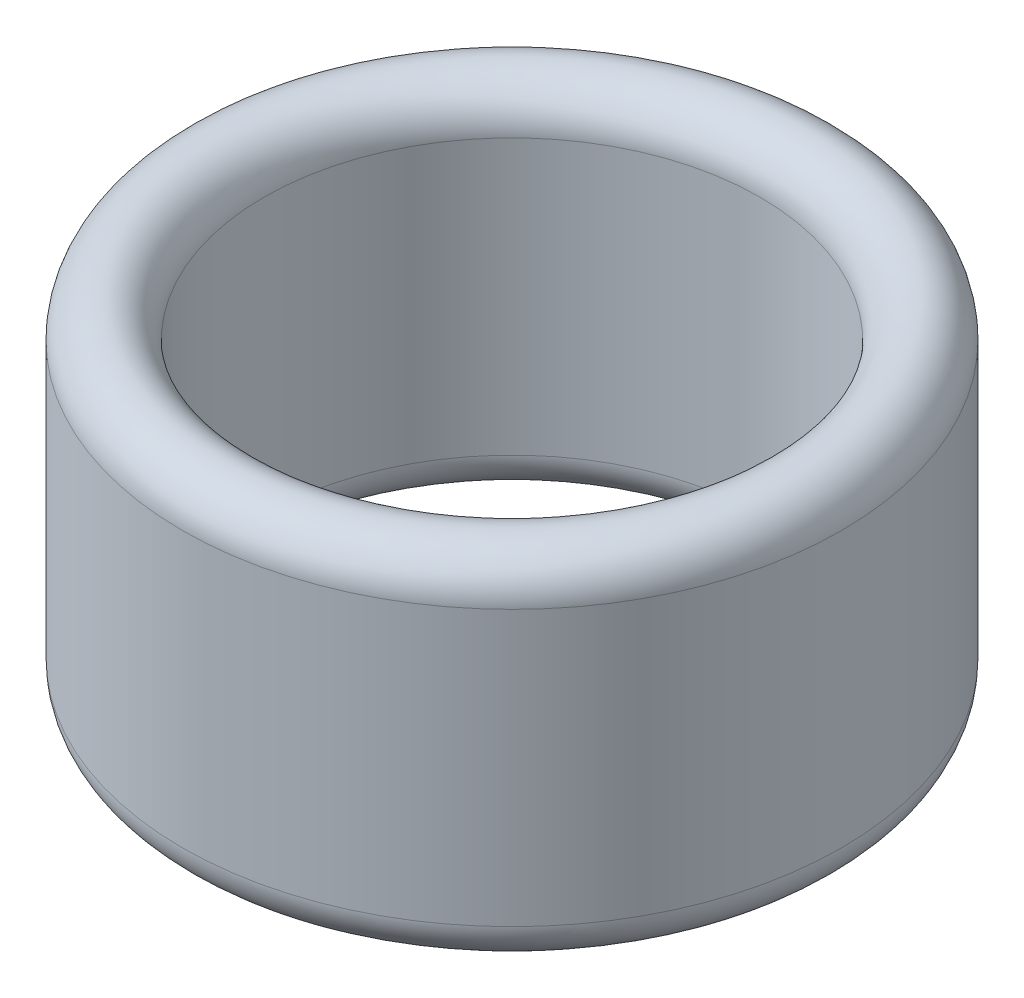
SolidWorks part; units mm, degrees
material "Plain Carbon Steel"
ref_plane "Front Plane" through (0, 0, 0) normal (0, 0, 1) x (1, 0, 0)
ref_plane "Top Plane" through (0, 0, 0) normal (0, 1, 0) x (1, 0, 0)
ref_plane "Right Plane" through (0, 0, 0) normal (1, 0, 0) x (0, 0, -1)
sketch "Sketch1" plane through (0, 0, 0) normal (0, 1, 0) x (1, 0, 0)
  circle A0 centre (0, 0) radius 3.5941
  dimension "D1" = 7.1882
extrude "Boss-Extrude1" add sketch "Sketch1" along normal blind 3.8862
sketch "Sketch2" plane through (0, 3.8862, 0) normal (0, 1, 0) x (1, 0, 0)
  circle A0 centre (0, 0) radius 2.7051
  circle A1 centre (0, 0) radius 3.5941 construction
  dimension "D1" = 0.889
extrude "Cut-Extrude1" cut sketch "Sketch2" against normal blind 3.8862
fillet "Fillet1" 2 edges at (0, 3.8862, 2.7051) (0, 3.8862, 3.5941) type full round first side face at (0, 0, 2.7051) second side face at (0, 3.8862, 3.5941) middle face at (0, 3.8862, 2.7051)
fillet "Fillet2" 2 edges at (0, 0, 3.5941) (0, 0, 2.7051) type full round first side face at (0, 3.4417, 3.5941) second side face at (0, 3.4417, 2.7051) middle face at (0, 0, 2.7051)
